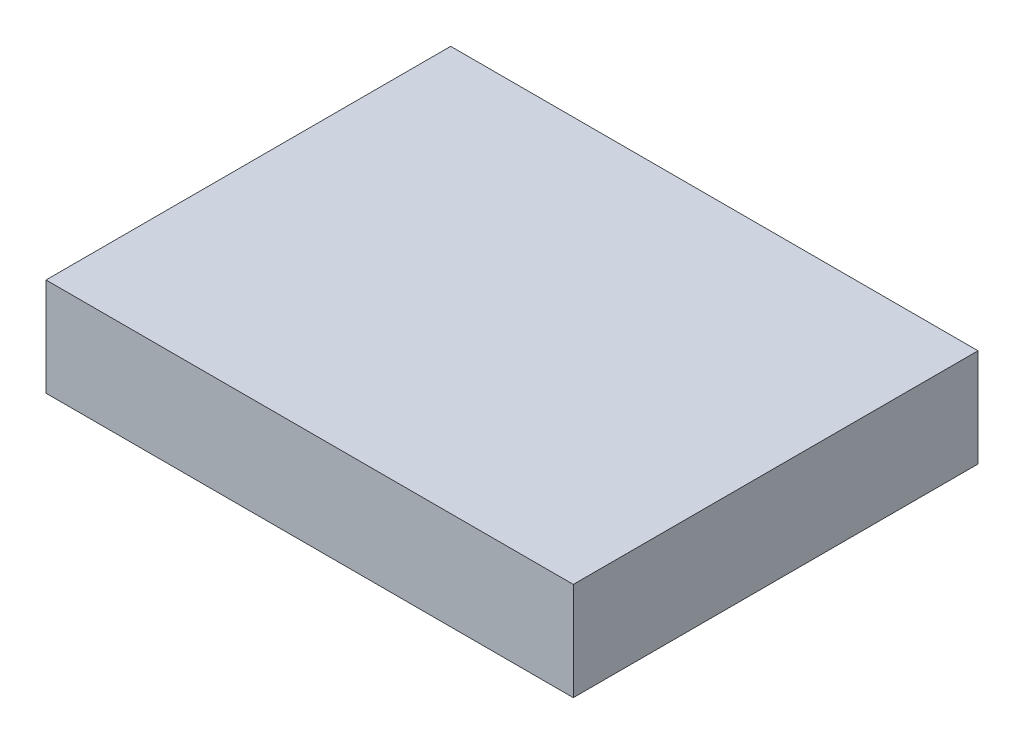
SolidWorks part; units mm, degrees
ref_plane "Front Plane" through (0, 0, 0) normal (0, 0, 1) x (1, 0, 0)
ref_plane "Top Plane" through (0, 0, 0) normal (0, 1, 0) x (1, 0, 0)
ref_plane "Right Plane" through (0, 0, 0) normal (1, 0, 0) x (0, 0, -1)
sketch "Sketch1" plane through (0, 0, 0) normal (0, 1, 0) x (1, 0, 0)
  line L1 (-43, -33) -> (43, -33)
  line L2 (-43, -33) -> (-43, 33)
  line L3 (-43, 33) -> (43, 33)
  line L4 (43, -33) -> (43, 33)
  line L5 (-43, -33) -> (43, 33) construction
  line L6 (-43, 33) -> (43, -33) construction
  point P0 (0, 0)
extrude "Boss-Extrude1" add sketch "Sketch1" along normal blind 16
sketch "Sketch2" plane through (0, 0, 0) normal (0, -1, 0) x (1, 0, 0)
  line L1 (-40.6, -30.6) -> (40.6, -30.6)
  line L2 (-40.6, -30.6) -> (-40.6, 30.6)
  line L3 (-40.6, 30.6) -> (40.6, 30.6)
  line L4 (40.6, -30.6) -> (40.6, 30.6)
  line L5 (-40.6, -30.6) -> (40.6, 30.6) construction
  line L6 (-40.6, 30.6) -> (40.6, -30.6) construction
  point P0 (0, 0)
extrude "Cut-Extrude1" cut sketch "Sketch2" against normal blind 13.6
sketch "Sketch3" plane through (0, 13.6, 0) normal (0, -1, 0) x (1, 0, 0)
  line L1 (1, 0.5) -> (26, 0.5)
  line L2 (1, 0.5) -> (1, 14.5)
  line L3 (1, 14.5) -> (26, 14.5)
  line L4 (26, 0.5) -> (26, 14.5)
  line L5 (1, 0.5) -> (26, 14.5) construction
  line L6 (1, 14.5) -> (26, 0.5) construction
  circle A0 centre (7, -13) radius 2.75
  circle A1 centre (7, -19) radius 2.75
  circle A2 centre (-3, -13) radius 1.25
  circle A3 centre (0, -13) radius 1
  circle A4 centre (-1, -10.2287) radius 1
  circle A5 centre (-4.6, -10.2287) radius 1.6
  circle A6 centre (-6.2, -13) radius 1.6
  circle A7 centre (-4.6, -15.7713) radius 1.6
  circle A8 centre (-1, -15.7713) radius 1
  circle A9 centre (21.5, -10.2287) radius 10.25
  circle A10 centre (24, 18.5) radius 5.25
  circle A11 centre (-8.2, -21) radius 1
  circle A12 centre (-1.8, -21) radius 0.8
  circle A13 centre (1, -21) radius 1.4
  point P0 (13.5, 7.5)
